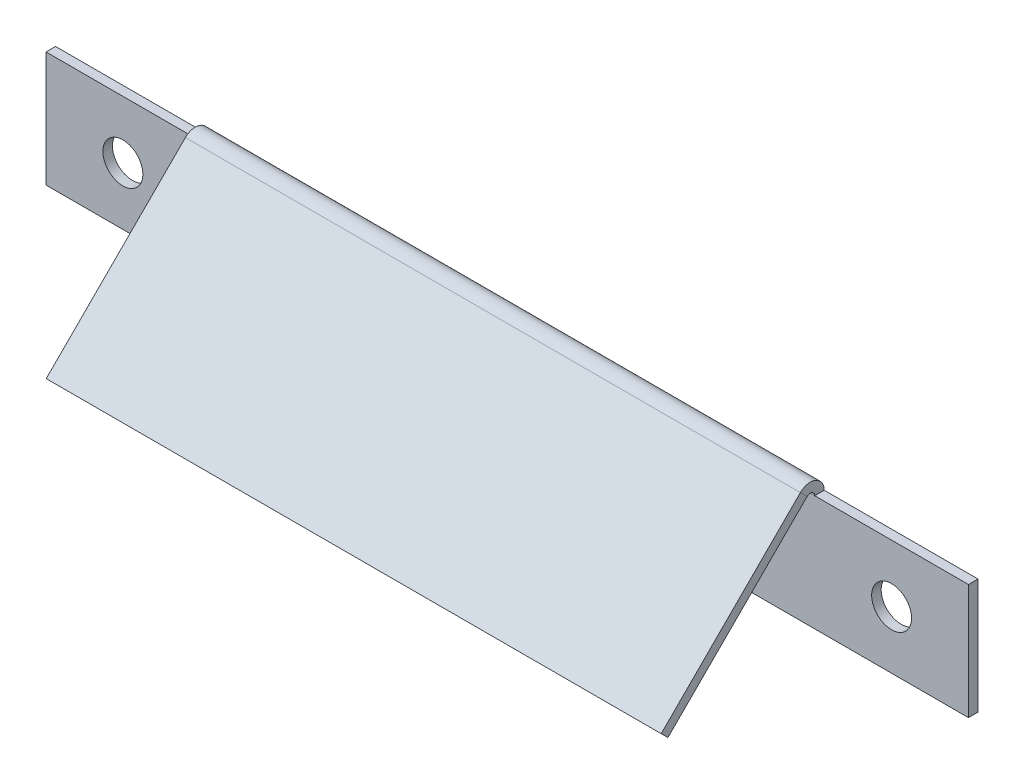
SolidWorks part; units mm, degrees
note: The reader was unsure of these and kept them because the rebuilt part matched: flange length of "Edge-Flange1".
ref_plane "Front Plane" through (0, 0, 0) normal (0, 0, 1) x (1, 0, 0)
ref_plane "Top Plane" through (0, 0, 0) normal (0, 1, 0) x (1, 0, 0)
ref_plane "Right Plane" through (0, 0, 0) normal (1, 0, 0) x (0, 0, -1)
sketch "Sketch3" plane through (0, 0, 0) normal (0, 0, 1) x (1, 0, 0)
  line L1 (-76.2, 9.525) -> (76.2, 9.525)
  line L2 (-76.2, 9.525) -> (-76.2, -9.525)
  line L3 (-76.2, -9.525) -> (76.2, -9.525)
  line L4 (76.2, 9.525) -> (76.2, -9.525)
  line L5 (-76.2, 9.525) -> (76.2, -9.525) construction
  line L6 (-76.2, -9.525) -> (76.2, 9.525) construction
  point P0 (0, 0)
  dimension "D1" = 152.4
  dimension "D2" = 19.05
base flange "Base-Flange1" sketch "Sketch3" thickness 1.5748 reverse thickness direction no parameters "D1"=0.7366
edge flange "Edge-Flange1" sketch "Sketch10" flange angle 45 flange length 38.1 flange position bend outside bend radius 0.7366 thickness 1.5748 relief rectangular parameters "D6"=10
sketch "Sketch10" plane through (0, 9.525, 0) normal (0, 0.7071, 0.7071) x (-1, 0, 0)
  line L0 (-76.2, 0) -> (76.2, 0) construction
  line L1 (-50.8, 0) -> (50.8, 0)
  line L2 (-50.8, 0) -> (-50.8, 34.2981)
  line L3 (-50.8, 34.2981) -> (50.8, 34.2981)
  line L4 (50.8, 34.2981) -> (50.8, 0)
  line L5 (-76.2, 13.4704) -> (-76.2, 0) construction
  line L6 (76.2, 0) -> (76.2, 13.4704) construction
  dimension "D1" = 25.4
  dimension "D2" = 25.4
bend "EdgeBend1" bend radius 0.7366 bend angle 135 parameters "D5"=1
hole_wizard "M6 Clearance Hole1" positions "Sketch13" profile "Sketch12" hole size "M6" standard "ANSI Metric" end condition through all
sketch "Sketch13" plane through (0, 0, 0) normal (0, 0, 1) x (1, 0, 0)
  line L3 (-76.2, 9.525) -> (-76.2, -9.525) construction
  line L5 (76.2, -9.525) -> (76.2, 9.525) construction
  point P0 (-63.5, 0)
  point P2 (63.5, 0)
  dimension "D1" = 12.7
  dimension "D2" = 12.7
  dimension "D3" = 127
sketch "Sketch12" plane through (-63.5, 0, 0) normal (1, 0, 0) x (0, -1, 0)
  line L0 (0, 0) -> (0, 1.5748)
  line L1 (0, 1.5748) -> (3.3, 1.5748)
  line L2 (3.3, 1.5748) -> (3.3, 0)
  line L5 (3.3, 0) -> (0, 0)
  line L11 (0, -6.35) -> (0, 107.95) construction
  dimension "Thru Hole Dia." = 6.6
  dimension "Thru Hole Depth" = 1.5748
sketch "Bend-Lines1" [suppressed] plane through (0, 0, 0) normal (0, 1, 0) x (1, 0, 0)
sketch "Bounding-Box1" [suppressed] plane through (0, 0, 0) normal (0, 1, 0) x (1, 0, 0)
sheet metal parameters "Sheet-Metal1" thickness 1.5748 parameters "D1"=0.7366
flat pattern "Flat-Pattern1" [suppressed]
sketch "Bend-Lines2" plane through (0, 0, 0) normal (0, 1, 0) x (1, 0, 0)
sketch3d "Bounding-Box2" [suppressed]
  line L0 (80.5909, -9.4655, 0) -> (-46.4091, -9.4655, 0) construction
  line L1 (80.5909, 15.9345, 0) -> (-46.4091, 15.9345, 0) construction
  line L2 (80.5909, -9.4655, 0) -> (80.5909, 15.9345, 0) construction
  line L3 (-46.4091, -9.4655, 0) -> (-46.4091, 15.9345, 0) construction
sheet metal parameters "Sheet-Metal2" thickness 1.5748 parameters "D1"=0.7366
flat pattern "Flat-Pattern1"
sketch "Bend-Lines2" plane through (0, 0, 0) normal (0, 0, 1) x (1, 0, 0)
  line L0 (50.8, 11.3204) -> (-50.8, 11.3204) construction
  line L1 (50.8, 11.3204) -> (-50.8, 11.3204) construction
sketch3d "Bounding-Box2" [suppressed]
  line L0 (-76.2, -9.525, 0) -> (76.2, -9.525, 0) construction
  line L1 (-76.2, 45.6356, 0) -> (76.2, 45.6356, 0) construction
  line L2 (-76.2, -9.525, 0) -> (-76.2, 45.6356, 0) construction
  line L3 (76.2, -9.525, 0) -> (76.2, 45.6356, 0) construction
bend of the flat pattern "Flatten-<EdgeBend1>1"
sheet metal parameters "Sheet-Metal3" thickness 1.5748 parameters "D1"=0.7366
flat pattern "Flat-Pattern1"
sketch "Bend-Lines2" plane through (0, 0, 0) normal (0, 0, 1) x (1, 0, 0)
  line L0 (50.8, 11.3204) -> (-50.8, 11.3204) construction
  line L1 (50.8, 11.3204) -> (-50.8, 11.3204) construction
sketch3d "Bounding-Box2" [suppressed]
  line L0 (-76.2, -9.525, 0) -> (76.2, -9.525, 0) construction
  line L1 (-76.2, 45.6356, 0) -> (76.2, 45.6356, 0) construction
  line L2 (-76.2, -9.525, 0) -> (-76.2, 45.6356, 0) construction
  line L3 (76.2, -9.525, 0) -> (76.2, 45.6356, 0) construction
bend of the flat pattern "Flatten-<EdgeBend1>1"
